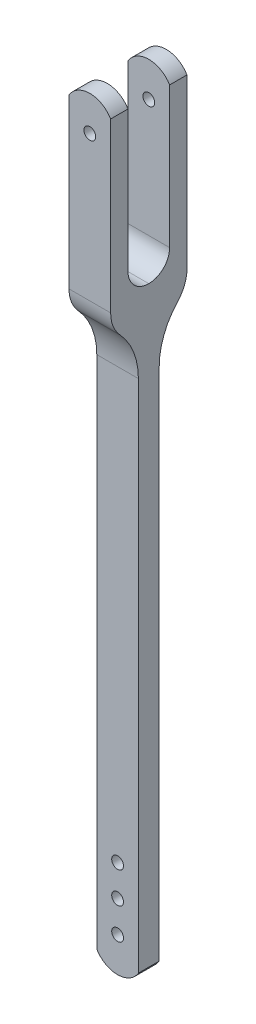
SolidWorks part; units mm, degrees
ref_plane "Front Plane" through (0, 0, 0) normal (0, 0, 1) x (1, 0, 0)
ref_plane "Top Plane" through (0, 0, 0) normal (0, 1, 0) x (1, 0, 0)
ref_plane "Right Plane" through (0, 0, 0) normal (1, 0, 0) x (0, 0, -1)
sketch "Esquisse1" plane through (0, 0, 0) normal (0, 0, 1) x (1, 0, 0)
  line L2 (-6.8285, -125.713) -> (-6.8285, 91.4981)
  line L4 (5.1715, -125.713) -> (5.1715, 91.4981)
  arc A0 (5.1715, 91.4981) -> (-6.8285, 91.4981) centre (-0.8285, 87.8925) ccw
  arc A1 (-6.8285, -125.713) -> (5.1715, -125.713) centre (-0.8285, -122.1075) ccw
  point P0 (0, 0)
  point P1 (-0.8285, -129.1075)
  point P3 (-0.8285, 94.8925)
  dimension "D3" = 14
  dimension "D4" = 14
  dimension "D1" = 224
  dimension "D2" = 12
extrude "Boss.-Extru.1" add sketch "Esquisse1" along normal blind 11 and the other way blind 11
ref_plane "Plane1" through (0, 94.8925, 0) normal (0, 1, 0) x (1, 0, 0)
sketch "Esquisse3" plane through (0, 94.8925, 0) normal (0, 1, 0) x (1, 0, 0)
  line L7 (-7, 0) -> (49993, 0) construction
  line L13 (-8.0887, -6) -> (8.4927, -6)
  line L14 (-8.0887, -6) -> (-8.0887, 6)
  line L15 (-8.0887, 6) -> (8.4927, 6)
  line L17 (8.4927, -6) -> (8.4927, 6)
  line L18 (-8.0887, -6) -> (8.4927, 6) construction
  line L19 (-8.0887, 6) -> (8.4927, -6) construction
  line L20 (5.1715, 11) -> (-6.8285, 11) construction
  line L21 (-6.8285, -11) -> (5.1715, -11) construction
  point P5 (0.202, 0)
  dimension "D1" = 5
  dimension "D2" = 5
extrude "Enlèv. mat.-Extru.2" cut sketch "Esquisse3" against normal blind 50
sketch "Sketch1" plane through (0, 0, 11) normal (0, 0, 1) x (1, 0, 0)
  line L1 (-0.8285, 90.5285) -> (-0.8285, -49909.4715) construction
  line L2 (-6.8285, 91.4981) -> (-6.8285, -125.713) construction
  line L3 (5.1715, -125.713) -> (5.1715, 91.4981) construction
  circle A0 centre (-0.8285, 84.8904) radius 1.7
  circle A1 centre (-0.8285, -119.1075) radius 1.7
  circle A3 centre (-0.8285, -110.1075) radius 1.7
  circle A5 centre (-0.8285, -101.1075) radius 1.7
  arc A6 (5.1715, 91.4981) -> (-6.8285, 91.4981) centre (-0.8285, 87.8925) ccw construction
  arc A7 (-6.8285, -125.713) -> (5.1715, -125.713) centre (-0.8285, -122.1075) ccw construction
  point P11 (-0.8285, 94.8925)
  point P16 (-0.8285, -129.1075)
  dimension "D1" = 3.4
  dimension "D2" = 10.0021
  dimension "D3" = 3.4
  dimension "D4" = 10
  dimension "D5" = 3.4
  dimension "D6" = 3.4
  dimension "D7" = 9
  dimension "D8" = 9
extrude "Cut-Extrude1" cut sketch "Sketch1" against normal up to surface (22 mm away) up to face at (-0.8285, -17.1075, -11)
sketch "Sketch4" plane through (0, 0, 11) normal (0, 0, 1) x (1, 0, 0)
  line L0 (-6.8285, 33.287) -> (-6.8285, -125.713)
  line L1 (-6.8285, 91.4981) -> (-6.8285, -125.713) construction
  line L2 (-6.8285, 33.287) -> (5.1715, 33.287)
  line L3 (5.1715, -125.713) -> (5.1715, 91.4981) construction
  line L4 (5.1715, 33.287) -> (5.1715, -125.713)
  arc A0 (-6.8285, -125.713) -> (5.1715, -125.713) centre (-0.8285, -125.713) ccw
  arc A1 (-6.8285, -125.713) -> (5.1715, -125.713) centre (-0.8285, -122.1075) ccw construction
  point P8 (-0.8285, -131.713)
  dimension "D1" = 165
extrude "Cut-Extrude2" cut sketch "Sketch4" against normal blind 8
mirror "Mirror1" about plane through (0, 0, 0) normal (0, 0, 1) of "Cut-Extrude2"
fillet "Fillet1" radius 10 2 edges at (-0.8285, 33.287, -11) (-0.8285, 33.287, 11)
fillet "Fillet2" radius 6 2 edges at (-0.8285, 44.8925, 6) (-0.8285, 44.8925, -6)
fillet "Fillet3" radius 20 2 edges at (-0.8285, 33.287, -3) (-0.8285, 33.287, 3)
equation "\"ScrewSize\"= 3.1mm"
